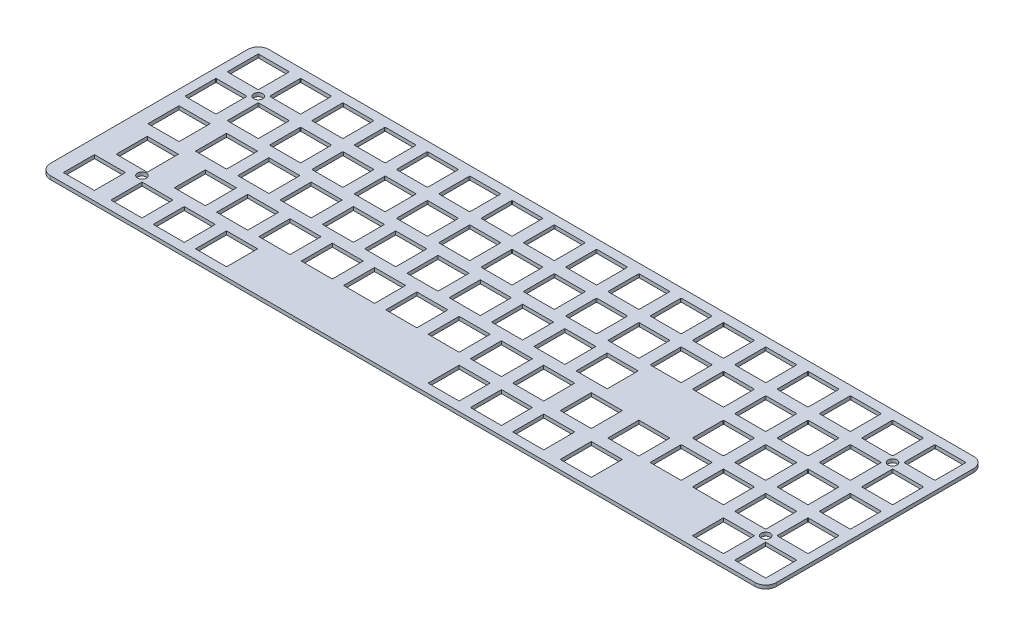
SolidWorks part; units mm, degrees
ref_plane "Front" through (0, 0, 0) normal (0, 0, 1) x (1, 0, 0)
ref_plane "Top" through (0, 0, 0) normal (0, 1, 0) x (1, 0, 0)
ref_plane "Right" through (0, 0, 0) normal (1, 0, 0) x (0, 0, -1)
sketch "Sketch1" plane through (0, 0, 0) normal (0, 1, 0) x (1, 0, 0)
  line L0 (-161.925, 28.575) -> (161.925, 28.575)
  line L1 (161.925, -47.625) -> (-161.925, -47.625)
  line L2 (161.925, -47.625) -> (161.925, 47.625)
  line L3 (161.925, 47.625) -> (-161.925, 47.625)
  line L4 (-161.925, -47.625) -> (-161.925, 47.625)
  line L5 (-123.825, 47.625) -> (-123.825, 28.575)
  line L6 (-104.775, 47.625) -> (-104.775, 28.575)
  line L7 (-142.875, 47.625) -> (-142.875, 28.575)
  line L8 (-85.725, 47.625) -> (-85.725, 28.575)
  line L9 (-66.675, 47.625) -> (-66.675, 28.575)
  line L10 (-47.625, 47.625) -> (-47.625, 28.575)
  line L11 (-28.575, 47.625) -> (-28.575, 28.575)
  line L12 (-9.525, 47.625) -> (-9.525, 28.575)
  line L13 (9.525, 47.625) -> (9.525, 28.575)
  line L14 (28.575, 47.625) -> (28.575, 28.575)
  line L15 (47.625, 47.625) -> (47.625, 28.575)
  line L16 (66.675, 47.625) -> (66.675, 28.575)
  line L17 (85.725, 47.625) -> (85.725, 28.575)
  line L18 (104.775, 47.625) -> (104.775, 28.575)
  line L19 (123.825, 47.625) -> (123.825, 28.575)
  line L20 (142.875, 47.625) -> (142.875, 28.575)
  line L21 (-142.875, 47.625) -> (-123.825, 47.625) construction
  line L22 (-161.925, 9.525) -> (161.925, 9.525)
  line L23 (-142.875, 28.575) -> (-142.875, 9.525)
  line L24 (-123.825, 28.575) -> (-123.825, 9.525)
  line L25 (-104.775, 28.575) -> (-104.775, 9.525)
  line L26 (-85.725, 28.575) -> (-85.725, 9.525)
  line L27 (-66.675, 28.575) -> (-66.675, 9.525)
  line L28 (-47.625, 28.575) -> (-47.625, 9.525)
  line L29 (-28.575, 28.575) -> (-28.575, 9.525)
  line L30 (-9.525, 28.575) -> (-9.525, 9.525)
  line L31 (9.525, 28.575) -> (9.525, 9.525)
  line L32 (28.575, 28.575) -> (28.575, 9.525)
  line L33 (47.625, 28.575) -> (47.625, 9.525)
  line L34 (66.675, 28.575) -> (66.675, 9.525)
  line L35 (85.725, 28.575) -> (85.725, 9.525)
  line L36 (104.775, 28.575) -> (104.775, 9.525)
  line L37 (123.825, 28.575) -> (123.825, 9.525)
  line L38 (142.875, 28.575) -> (142.875, 9.525)
  line L39 (-142.875, 28.575) -> (-123.825, 28.575) construction
  line L40 (-161.925, -9.525) -> (161.925, -9.525)
  line L41 (-161.925, -28.575) -> (161.925, -28.575)
  line L42 (-138.1125, 9.525) -> (-138.1125, -9.525)
  line L43 (-128.5875, -9.525) -> (-128.5875, -28.575)
  line L44 (-138.1125, -28.575) -> (-138.1125, -47.625)
  line L45 (-119.0625, 9.525) -> (-119.0625, -9.525)
  line L46 (-100.0125, 9.525) -> (-100.0125, -9.525)
  line L47 (-80.9625, 9.525) -> (-80.9625, -9.525)
  line L48 (-61.9125, 9.525) -> (-61.9125, -9.525)
  line L49 (-42.8625, 9.525) -> (-42.8625, -9.525)
  line L50 (-23.8125, 9.525) -> (-23.8125, -9.525)
  line L51 (-4.7625, 9.525) -> (-4.7625, -9.525)
  line L52 (14.2875, 9.525) -> (14.2875, -9.525)
  line L53 (33.3375, 9.525) -> (33.3375, -9.525)
  line L54 (-138.1125, 9.525) -> (-119.0625, 9.525) construction
  line L55 (52.3875, 9.525) -> (52.3875, -9.525)
  line L56 (85.725, 9.525) -> (85.725, -9.525)
  line L57 (-109.5375, -9.525) -> (-109.5375, -28.575)
  line L58 (-90.4875, -9.525) -> (-90.4875, -28.575)
  line L59 (-71.4375, -9.525) -> (-71.4375, -28.575)
  line L60 (-52.3875, -9.525) -> (-52.3875, -28.575)
  line L61 (-33.3375, -9.525) -> (-33.3375, -28.575)
  line L62 (-14.2875, -9.525) -> (-14.2875, -28.575)
  line L63 (4.7625, -9.525) -> (4.7625, -28.575)
  line L64 (23.8125, -9.525) -> (23.8125, -28.575)
  line L65 (42.8625, -9.525) -> (42.8625, -28.575)
  line L66 (-128.5875, -9.525) -> (-109.5375, -9.525) construction
  line L67 (66.675, -9.525) -> (66.675, -28.575)
  line L68 (85.725, -9.525) -> (85.725, -28.575)
  line L69 (-119.0625, -28.575) -> (-119.0625, -47.625)
  line L70 (-100.0125, -28.575) -> (-100.0125, -47.625)
  line L71 (-80.9625, -28.575) -> (-80.9625, -47.625)
  line L72 (-138.1125, -28.575) -> (-119.0625, -28.575) construction
  line L73 (-47.625, -28.575) -> (-47.625, -47.625)
  line L74 (4.7625, -28.575) -> (4.7625, -47.625)
  line L75 (23.8125, -28.575) -> (23.8125, -47.625)
  line L76 (42.8625, -28.575) -> (42.8625, -47.625)
  line L77 (61.9125, -28.575) -> (61.9125, -47.625)
  line L78 (85.725, -28.575) -> (85.725, -47.625)
  line L79 (104.775, 9.525) -> (104.775, -9.525)
  line L80 (104.775, -9.525) -> (104.775, -28.575)
  line L81 (123.825, 9.525) -> (123.825, -9.525)
  line L82 (123.825, -9.525) -> (123.825, -28.575)
  line L83 (123.825, -28.575) -> (123.825, -47.625)
  line L84 (142.875, 9.525) -> (142.875, -9.525)
  line L85 (142.875, -9.525) -> (142.875, -28.575)
  line L86 (142.875, -28.575) -> (142.875, -47.625)
  line L87 (-161.925, 47.625) -> (-142.875, 28.575) construction
  line L88 (-142.875, 28.575) -> (-161.925, 9.525) construction
  line L89 (-161.925, 9.525) -> (-138.1125, -9.525) construction
  line L90 (-138.1125, -9.525) -> (-119.0625, 9.525) construction
  line L91 (-119.0625, 9.525) -> (-100.0125, -9.525) construction
  line L92 (-100.0125, -9.525) -> (-80.9625, 9.525) construction
  line L93 (-80.9625, 9.525) -> (-61.9125, -9.525) construction
  line L94 (-61.9125, -9.525) -> (-42.8625, 9.525) construction
  line L95 (-42.8625, 9.525) -> (-23.8125, -9.525) construction
  line L96 (-23.8125, -9.525) -> (-4.7625, 9.525) construction
  line L97 (-4.7625, 9.525) -> (14.2875, -9.525) construction
  line L98 (14.2875, -9.525) -> (33.3375, 9.525) construction
  line L99 (33.3375, 9.525) -> (52.3875, -9.525) construction
  line L100 (52.3875, -9.525) -> (85.725, 9.525) construction
  line L101 (85.725, 9.525) -> (104.775, -9.525) construction
  line L102 (104.775, -9.525) -> (85.725, -28.575) construction
  line L103 (85.725, -47.625) -> (123.825, -28.575) construction
  line L104 (85.725, -28.575) -> (123.825, -47.625) construction
  line L105 (123.825, -28.575) -> (104.775, -9.525) construction
  line L106 (104.775, -9.525) -> (123.825, 9.525) construction
  line L107 (123.825, 9.525) -> (104.775, 28.575) construction
  line L108 (104.775, 28.575) -> (123.825, 47.625) construction
  line L109 (123.825, 47.625) -> (142.875, 28.575) construction
  line L110 (142.875, 28.575) -> (123.825, 9.525) construction
  line L111 (123.825, 9.525) -> (142.875, -9.525) construction
  line L112 (142.875, -9.525) -> (123.825, -28.575) construction
  line L113 (123.825, -28.575) -> (142.875, -47.625) construction
  line L114 (142.875, -47.625) -> (161.925, -28.575) construction
  line L115 (161.925, -28.575) -> (142.875, -9.525) construction
  line L116 (142.875, -9.525) -> (161.925, 9.525) construction
  line L117 (161.925, 9.525) -> (142.875, 28.575) construction
  line L118 (142.875, 28.575) -> (161.925, 47.625) construction
  line L119 (161.925, -47.625) -> (142.875, -28.575) construction
  line L120 (142.875, -28.575) -> (123.825, -47.625) construction
  line L121 (85.725, -47.625) -> (61.9125, -28.575) construction
  line L122 (61.9125, -28.575) -> (42.8625, -47.625) construction
  line L123 (42.8625, -47.625) -> (23.8125, -28.575) construction
  line L124 (23.8125, -28.575) -> (42.8625, -9.525) construction
  line L125 (42.8625, -9.525) -> (66.675, -28.575) construction
  line L126 (66.675, -28.575) -> (85.725, -9.525) construction
  line L127 (85.725, -9.525) -> (104.775, -28.575) construction
  line L128 (104.775, -28.575) -> (123.825, -9.525) construction
  line L129 (123.825, -9.525) -> (142.875, -28.575) construction
  line L130 (142.875, -28.575) -> (161.925, -9.525) construction
  line L131 (161.925, -9.525) -> (142.875, 9.525) construction
  line L132 (142.875, 9.525) -> (123.825, -9.525) construction
  line L133 (123.825, -9.525) -> (104.775, 9.525) construction
  line L134 (104.775, 9.525) -> (85.725, -9.525) construction
  line L135 (85.725, -9.525) -> (52.3875, 9.525) construction
  line L136 (52.3875, 9.525) -> (33.3375, -9.525) construction
  line L137 (33.3375, -9.525) -> (14.2875, 9.525) construction
  line L138 (14.2875, 9.525) -> (-4.7625, -9.525) construction
  line L139 (-4.7625, -9.525) -> (-23.8125, 9.525) construction
  line L140 (-23.8125, 9.525) -> (-42.8625, -9.525) construction
  line L141 (-42.8625, -9.525) -> (-61.9125, 9.525) construction
  line L142 (-61.9125, 9.525) -> (-80.9625, -9.525) construction
  line L143 (-80.9625, -9.525) -> (-100.0125, 9.525) construction
  line L144 (-100.0125, 9.525) -> (-119.0625, -9.525) construction
  line L145 (-119.0625, -9.525) -> (-138.1125, 9.525) construction
  line L146 (-138.1125, 9.525) -> (-161.925, -9.525) construction
  line L147 (-161.925, -9.525) -> (-128.5875, -28.575) construction
  line L148 (-128.5875, -28.575) -> (-109.5375, -9.525) construction
  line L149 (-109.5375, -9.525) -> (-90.4875, -28.575) construction
  line L150 (-90.4875, -28.575) -> (-71.4375, -9.525) construction
  line L151 (-71.4375, -9.525) -> (-52.3875, -28.575) construction
  line L152 (-52.3875, -28.575) -> (-33.3375, -9.525) construction
  line L153 (-33.3375, -9.525) -> (-14.2875, -28.575) construction
  line L154 (-14.2875, -28.575) -> (4.7625, -9.525) construction
  line L155 (4.7625, -9.525) -> (23.8125, -28.575) construction
  line L156 (23.8125, -28.575) -> (4.7625, -47.625) construction
  line L157 (4.7625, -47.625) -> (-47.625, -28.575) construction
  line L158 (-47.625, -28.575) -> (-80.9625, -47.625) construction
  line L159 (-80.9625, -47.625) -> (-100.0125, -28.575) construction
  line L160 (-100.0125, -28.575) -> (-119.0625, -47.625) construction
  line L161 (-119.0625, -47.625) -> (-138.1125, -28.575) construction
  line L162 (-138.1125, -28.575) -> (-161.925, -47.625) construction
  line L163 (-161.925, -28.575) -> (-138.1125, -47.625) construction
  line L164 (-138.1125, -47.625) -> (-119.0625, -28.575) construction
  line L165 (-119.0625, -28.575) -> (-100.0125, -47.625) construction
  line L166 (-100.0125, -47.625) -> (-80.9625, -28.575) construction
  line L167 (-80.9625, -28.575) -> (-47.625, -47.625) construction
  line L168 (-47.625, -47.625) -> (4.7625, -28.575) construction
  line L169 (4.7625, -28.575) -> (23.8125, -47.625) construction
  line L170 (23.8125, -47.625) -> (42.8625, -28.575) construction
  line L171 (42.8625, -28.575) -> (61.9125, -47.625) construction
  line L172 (61.9125, -47.625) -> (85.725, -28.575) construction
  line L173 (85.725, -28.575) -> (66.675, -9.525) construction
  line L174 (66.675, -9.525) -> (42.8625, -28.575) construction
  line L175 (42.8625, -28.575) -> (23.8125, -9.525) construction
  line L176 (23.8125, -9.525) -> (4.7625, -28.575) construction
  line L177 (4.7625, -28.575) -> (-14.2875, -9.525) construction
  line L178 (-14.2875, -9.525) -> (-33.3375, -28.575) construction
  line L179 (-33.3375, -28.575) -> (-52.3875, -9.525) construction
  line L180 (-52.3875, -9.525) -> (-71.4375, -28.575) construction
  line L181 (-71.4375, -28.575) -> (-90.4875, -9.525) construction
  line L182 (-90.4875, -9.525) -> (-109.5375, -28.575) construction
  line L183 (-109.5375, -28.575) -> (-128.5875, -9.525) construction
  line L184 (-128.5875, -9.525) -> (-161.925, -28.575) construction
  line L185 (161.925, 28.575) -> (142.875, 9.525) construction
  line L186 (142.875, 9.525) -> (123.825, 28.575) construction
  line L187 (123.825, 28.575) -> (104.775, 9.525) construction
  line L188 (104.775, 9.525) -> (85.725, 28.575) construction
  line L189 (85.725, 28.575) -> (66.675, 9.525) construction
  line L190 (66.675, 9.525) -> (47.625, 28.575) construction
  line L191 (47.625, 28.575) -> (28.575, 9.525) construction
  line L192 (28.575, 9.525) -> (9.525, 28.575) construction
  line L193 (9.525, 28.575) -> (-9.525, 9.525) construction
  line L194 (-9.525, 9.525) -> (-28.575, 28.575) construction
  line L195 (-28.575, 28.575) -> (-47.625, 9.525) construction
  line L196 (-47.625, 9.525) -> (-66.675, 28.575) construction
  line L197 (-66.675, 28.575) -> (-85.725, 9.525) construction
  line L198 (-85.725, 9.525) -> (-104.775, 28.575) construction
  line L199 (-104.775, 28.575) -> (-123.825, 9.525) construction
  line L200 (-123.825, 9.525) -> (-142.875, 28.575) construction
  line L201 (-161.925, 28.575) -> (-142.875, 9.525) construction
  line L202 (-142.875, 9.525) -> (-123.825, 28.575) construction
  line L203 (-123.825, 28.575) -> (-104.775, 9.525) construction
  line L204 (-104.775, 9.525) -> (-85.725, 28.575) construction
  line L205 (-85.725, 28.575) -> (-66.675, 9.525) construction
  line L206 (-66.675, 9.525) -> (-47.625, 28.575) construction
  line L207 (-47.625, 28.575) -> (-28.575, 9.525) construction
  line L208 (-28.575, 9.525) -> (-9.525, 28.575) construction
  line L209 (-9.525, 28.575) -> (9.525, 9.525) construction
  line L210 (9.525, 9.525) -> (28.575, 28.575) construction
  line L211 (28.575, 28.575) -> (47.625, 9.525) construction
  line L212 (47.625, 9.525) -> (66.675, 28.575) construction
  line L213 (66.675, 28.575) -> (85.725, 9.525) construction
  line L214 (85.725, 9.525) -> (104.775, 28.575) construction
  line L215 (161.925, 28.575) -> (142.875, 47.625) construction
  line L216 (142.875, 47.625) -> (123.825, 28.575) construction
  line L217 (123.825, 28.575) -> (104.775, 47.625) construction
  line L218 (104.775, 47.625) -> (85.725, 28.575) construction
  line L219 (85.725, 28.575) -> (66.675, 47.625) construction
  line L220 (66.675, 47.625) -> (47.625, 28.575) construction
  line L221 (47.625, 28.575) -> (28.575, 47.625) construction
  line L222 (28.575, 47.625) -> (9.525, 28.575) construction
  line L223 (9.525, 28.575) -> (-9.525, 47.625) construction
  line L224 (-9.525, 47.625) -> (-28.575, 28.575) construction
  line L225 (-28.575, 28.575) -> (-47.625, 47.625) construction
  line L226 (-47.625, 47.625) -> (-66.675, 28.575) construction
  line L227 (-66.675, 28.575) -> (-85.725, 47.625) construction
  line L228 (-85.725, 47.625) -> (-104.775, 28.575) construction
  line L229 (-104.775, 28.575) -> (-123.825, 47.625) construction
  line L230 (-123.825, 47.625) -> (-142.875, 28.575) construction
  line L231 (-161.925, 28.575) -> (-142.875, 47.625) construction
  line L232 (-142.875, 47.625) -> (-123.825, 28.575) construction
  line L233 (-123.825, 28.575) -> (-104.775, 47.625) construction
  line L234 (-104.775, 47.625) -> (-85.725, 28.575) construction
  line L235 (-85.725, 28.575) -> (-66.675, 47.625) construction
  line L236 (-66.675, 47.625) -> (-47.625, 28.575) construction
  line L237 (-47.625, 28.575) -> (-28.575, 47.625) construction
  line L238 (-28.575, 47.625) -> (-9.525, 28.575) construction
  line L239 (-9.525, 28.575) -> (9.525, 47.625) construction
  line L240 (9.525, 47.625) -> (28.575, 28.575) construction
  line L241 (28.575, 28.575) -> (47.625, 47.625) construction
  line L242 (47.625, 47.625) -> (66.675, 28.575) construction
  line L243 (66.675, 28.575) -> (85.725, 47.625) construction
  line L244 (85.725, 47.625) -> (104.775, 28.575) construction
  line L245 (160.147, 50.6095) -> (-160.147, 50.6095)
  line L246 (164.9095, 45.847) -> (164.9095, -45.847)
  line L247 (160.147, -50.6095) -> (-160.147, -50.6095)
  line L248 (-164.9095, 45.847) -> (-164.9095, -45.847)
  arc A0 (164.9095, 45.847) -> (160.147, 50.6095) centre (160.147, 45.847) ccw
  arc A1 (160.147, -50.6095) -> (164.9095, -45.847) centre (160.147, -45.847) ccw
  arc A2 (-164.9095, -45.847) -> (-160.147, -50.6095) centre (-160.147, -45.847) ccw
  arc A3 (-160.147, 50.6095) -> (-164.9095, 45.847) centre (-160.147, 45.847) ccw
  point P145 (0, 0)
  point P146 (104.775, -38.1)
  point P147 (-152.4, 38.1)
  point P148 (-152.4, 19.05)
  point P149 (-150.0188, 0)
  point P150 (-145.2562, -19.05)
  point P151 (-150.0188, -38.1)
  point P152 (-128.5875, -38.1)
  point P153 (-119.0625, -19.05)
  point P154 (-128.5875, 0)
  point P155 (-133.35, 19.05)
  point P156 (-133.35, 38.1)
  point P157 (-114.3, 38.1)
  point P158 (-114.3, 19.05)
  point P159 (-109.5375, 0)
  point P160 (-100.0125, -19.05)
  point P161 (-90.4875, -38.1)
  point P162 (-109.5375, -38.1)
  point P163 (-64.2938, -38.1)
  point P164 (-21.4312, -38.1)
  point P165 (14.2875, -38.1)
  point P166 (33.3375, -38.1)
  point P167 (52.3875, -38.1)
  point P168 (73.8188, -38.1)
  point P169 (133.35, -38.1)
  point P170 (152.4, -38.1)
  point P171 (152.4, -19.05)
  point P172 (133.35, -19.05)
  point P173 (114.3, -19.05)
  point P174 (95.25, -19.05)
  point P175 (76.2, -19.05)
  point P176 (54.7687, -19.05)
  point P177 (33.3375, -19.05)
  point P178 (14.2875, -19.05)
  point P179 (-4.7625, -19.05)
  point P180 (-23.8125, -19.05)
  point P181 (-42.8625, -19.05)
  point P182 (-61.9125, -19.05)
  point P183 (-80.9625, -19.05)
  point P184 (-90.4875, 0)
  point P185 (-71.4375, 0)
  point P186 (-52.3875, 0)
  point P187 (-33.3375, 0)
  point P188 (-14.2875, 0)
  point P189 (4.7625, 0)
  point P190 (23.8125, 0)
  point P191 (42.8625, 0)
  point P192 (69.0563, 0)
  point P193 (95.25, 0)
  point P194 (114.3, 0)
  point P195 (133.35, 0)
  point P196 (152.4, 0)
  point P197 (152.4, 19.05)
  point P198 (133.35, 19.05)
  point P199 (114.3, 19.05)
  point P200 (95.25, 19.05)
  point P201 (76.2, 19.05)
  point P202 (57.15, 19.05)
  point P203 (38.1, 19.05)
  point P204 (19.05, 19.05)
  point P205 (0, 19.05)
  point P206 (-19.05, 19.05)
  point P207 (-38.1, 19.05)
  point P208 (-57.15, 19.05)
  point P209 (-76.2, 19.05)
  point P210 (-95.25, 19.05)
  point P211 (-95.25, 38.1)
  point P212 (-76.2, 38.1)
  point P213 (-57.15, 38.1)
  point P214 (-38.1, 38.1)
  point P215 (-19.05, 38.1)
  point P216 (0, 38.1)
  point P217 (19.05, 38.1)
  point P218 (38.1, 38.1)
  point P219 (57.15, 38.1)
  point P220 (76.2, 38.1)
  point P221 (95.25, 38.1)
  point P222 (114.3, 38.1)
  point P223 (133.35, 38.1)
  point P224 (152.4, 38.1)
  point P225 (-152.4, 38.1)
  point P226 (0, 0)
sketch "Sketch2" plane through (0, 0, 0) normal (0, 1, 0) x (1, 0, 0)
  line L0 (-161.925, 28.575) -> (-142.875, 47.625) construction
  line L1 (-145.7071, 45.0977) -> (-159.0929, 45.0977)
  line L2 (-145.4023, 44.7929) -> (-145.4023, 31.4071)
  line L3 (-145.7071, 31.1023) -> (-159.0929, 31.1023)
  line L4 (-159.3977, 44.7929) -> (-159.3977, 31.4071)
  line L5 (-152.4, 31.1023) -> (-152.4, 45.0977) construction
  line L6 (-145.4023, 38.1) -> (-159.3977, 38.1) construction
  line L7 (-126.3523, 38.1) -> (-140.3477, 38.1) construction
  line L8 (-133.35, 31.1023) -> (-133.35, 45.0977) construction
  line L9 (-126.6571, 45.0977) -> (-140.0429, 45.0977)
  line L10 (-126.3523, 44.7929) -> (-126.3523, 31.4071)
  line L11 (-140.3477, 44.7929) -> (-140.3477, 31.4071)
  line L12 (-126.6571, 31.1023) -> (-140.0429, 31.1023)
  line L13 (-107.3023, 38.1) -> (-121.2977, 38.1) construction
  line L14 (-114.3, 31.1023) -> (-114.3, 45.0977) construction
  line L15 (-107.6071, 45.0977) -> (-120.9929, 45.0977)
  line L16 (-107.3023, 44.7929) -> (-107.3023, 31.4071)
  line L17 (-121.2977, 44.7929) -> (-121.2977, 31.4071)
  line L18 (-107.6071, 31.1023) -> (-120.9929, 31.1023)
  line L19 (-88.2523, 38.1) -> (-102.2477, 38.1) construction
  line L20 (-95.25, 31.1023) -> (-95.25, 45.0977) construction
  line L21 (-88.5571, 45.0977) -> (-101.9429, 45.0977)
  line L22 (-88.2523, 44.7929) -> (-88.2523, 31.4071)
  line L23 (-102.2477, 44.7929) -> (-102.2477, 31.4071)
  line L24 (-88.5571, 31.1023) -> (-101.9429, 31.1023)
  line L25 (-69.2023, 38.1) -> (-83.1977, 38.1) construction
  line L26 (-76.2, 31.1023) -> (-76.2, 45.0977) construction
  line L27 (-69.5071, 45.0977) -> (-82.8929, 45.0977)
  line L28 (-69.2023, 44.7929) -> (-69.2023, 31.4071)
  line L29 (-83.1977, 44.7929) -> (-83.1977, 31.4071)
  line L30 (-69.5071, 31.1023) -> (-82.8929, 31.1023)
  line L31 (-50.1523, 38.1) -> (-64.1477, 38.1) construction
  line L32 (-57.15, 31.1023) -> (-57.15, 45.0977) construction
  line L33 (-50.4571, 45.0977) -> (-63.8429, 45.0977)
  line L34 (-50.1523, 44.7929) -> (-50.1523, 31.4071)
  line L35 (-64.1477, 44.7929) -> (-64.1477, 31.4071)
  line L36 (-50.4571, 31.1023) -> (-63.8429, 31.1023)
  line L37 (-31.1023, 38.1) -> (-45.0977, 38.1) construction
  line L38 (-38.1, 31.1023) -> (-38.1, 45.0977) construction
  line L39 (-31.4071, 45.0977) -> (-44.7929, 45.0977)
  line L40 (-31.1023, 44.7929) -> (-31.1023, 31.4071)
  line L41 (-45.0977, 44.7929) -> (-45.0977, 31.4071)
  line L42 (-31.4071, 31.1023) -> (-44.7929, 31.1023)
  line L43 (-12.0523, 38.1) -> (-26.0477, 38.1) construction
  line L44 (-19.05, 31.1023) -> (-19.05, 45.0977) construction
  line L45 (-12.3571, 45.0977) -> (-25.7429, 45.0977)
  line L46 (-12.0523, 44.7929) -> (-12.0523, 31.4071)
  line L47 (-26.0477, 44.7929) -> (-26.0477, 31.4071)
  line L48 (-12.3571, 31.1023) -> (-25.7429, 31.1023)
  line L49 (6.9977, 38.1) -> (-6.9977, 38.1) construction
  line L50 (0, 31.1023) -> (0, 45.0977) construction
  line L51 (6.6929, 45.0977) -> (-6.6929, 45.0977)
  line L52 (6.9977, 44.7929) -> (6.9977, 31.4071)
  line L53 (-6.9977, 44.7929) -> (-6.9977, 31.4071)
  line L54 (6.6929, 31.1023) -> (-6.6929, 31.1023)
  line L55 (26.0477, 38.1) -> (12.0523, 38.1) construction
  line L56 (19.05, 31.1023) -> (19.05, 45.0977) construction
  line L57 (25.7429, 45.0977) -> (12.3571, 45.0977)
  line L58 (26.0477, 44.7929) -> (26.0477, 31.4071)
  line L59 (12.0523, 44.7929) -> (12.0523, 31.4071)
  line L60 (25.7429, 31.1023) -> (12.3571, 31.1023)
  line L61 (45.0977, 38.1) -> (31.1023, 38.1) construction
  line L62 (38.1, 31.1023) -> (38.1, 45.0977) construction
  line L63 (44.7929, 45.0977) -> (31.4071, 45.0977)
  line L64 (45.0977, 44.7929) -> (45.0977, 31.4071)
  line L65 (31.1023, 44.7929) -> (31.1023, 31.4071)
  line L66 (44.7929, 31.1023) -> (31.4071, 31.1023)
  line L67 (64.1477, 38.1) -> (50.1523, 38.1) construction
  line L68 (57.15, 31.1023) -> (57.15, 45.0977) construction
  line L69 (63.8429, 45.0977) -> (50.4571, 45.0977)
  line L70 (64.1477, 44.7929) -> (64.1477, 31.4071)
  line L71 (50.1523, 44.7929) -> (50.1523, 31.4071)
  line L72 (63.8429, 31.1023) -> (50.4571, 31.1023)
  line L73 (83.1977, 38.1) -> (69.2023, 38.1) construction
  line L74 (76.2, 31.1023) -> (76.2, 45.0977) construction
  line L75 (82.8929, 45.0977) -> (69.5071, 45.0977)
  line L76 (83.1977, 44.7929) -> (83.1977, 31.4071)
  line L77 (69.2023, 44.7929) -> (69.2023, 31.4071)
  line L78 (82.8929, 31.1023) -> (69.5071, 31.1023)
  line L79 (102.2477, 38.1) -> (88.2523, 38.1) construction
  line L80 (95.25, 31.1023) -> (95.25, 45.0977) construction
  line L81 (101.9429, 45.0977) -> (88.5571, 45.0977)
  line L82 (102.2477, 44.7929) -> (102.2477, 31.4071)
  line L83 (88.2523, 44.7929) -> (88.2523, 31.4071)
  line L84 (101.9429, 31.1023) -> (88.5571, 31.1023)
  line L85 (121.2977, 38.1) -> (107.3023, 38.1) construction
  line L86 (114.3, 31.1023) -> (114.3, 45.0977) construction
  line L87 (120.9929, 45.0977) -> (107.6071, 45.0977)
  line L88 (121.2977, 44.7929) -> (121.2977, 31.4071)
  line L89 (107.3023, 44.7929) -> (107.3023, 31.4071)
  line L90 (120.9929, 31.1023) -> (107.6071, 31.1023)
  line L91 (140.3477, 38.1) -> (126.3523, 38.1) construction
  line L92 (133.35, 31.1023) -> (133.35, 45.0977) construction
  line L93 (140.0429, 45.0977) -> (126.6571, 45.0977)
  line L94 (140.3477, 44.7929) -> (140.3477, 31.4071)
  line L95 (126.3523, 44.7929) -> (126.3523, 31.4071)
  line L96 (140.0429, 31.1023) -> (126.6571, 31.1023)
  line L97 (159.3977, 38.1) -> (145.4023, 38.1) construction
  line L98 (152.4, 31.1023) -> (152.4, 45.0977) construction
  line L99 (159.0929, 45.0977) -> (145.7071, 45.0977)
  line L100 (159.3977, 44.7929) -> (159.3977, 31.4071)
  line L101 (145.4023, 44.7929) -> (145.4023, 31.4071)
  line L102 (159.0929, 31.1023) -> (145.7071, 31.1023)
  line L103 (-126.3523, 19.05) -> (-140.3477, 19.05) construction
  line L104 (-133.35, 12.0523) -> (-133.35, 26.0477) construction
  line L105 (-126.6571, 26.0477) -> (-140.0429, 26.0477)
  line L106 (-126.3523, 25.7429) -> (-126.3523, 12.3571)
  line L107 (-140.3477, 25.7429) -> (-140.3477, 12.3571)
  line L108 (-126.6571, 12.0523) -> (-140.0429, 12.0523)
  line L109 (-107.3023, 19.05) -> (-121.2977, 19.05) construction
  line L110 (-114.3, 12.0523) -> (-114.3, 26.0477) construction
  line L111 (-107.6071, 26.0477) -> (-120.9929, 26.0477)
  line L112 (-107.3023, 25.7429) -> (-107.3023, 12.3571)
  line L113 (-121.2977, 25.7429) -> (-121.2977, 12.3571)
  line L114 (-107.6071, 12.0523) -> (-120.9929, 12.0523)
  line L115 (-88.2523, 19.05) -> (-102.2477, 19.05) construction
  line L116 (-95.25, 12.0523) -> (-95.25, 26.0477) construction
  line L117 (-88.5571, 26.0477) -> (-101.9429, 26.0477)
  line L118 (-88.2523, 25.7429) -> (-88.2523, 12.3571)
  line L119 (-102.2477, 25.7429) -> (-102.2477, 12.3571)
  line L120 (-88.5571, 12.0523) -> (-101.9429, 12.0523)
  line L121 (-69.2023, 19.05) -> (-83.1977, 19.05) construction
  line L122 (-76.2, 12.0523) -> (-76.2, 26.0477) construction
  line L123 (-69.5071, 26.0477) -> (-82.8929, 26.0477)
  line L124 (-69.2023, 25.7429) -> (-69.2023, 12.3571)
  line L125 (-83.1977, 25.7429) -> (-83.1977, 12.3571)
  line L126 (-69.5071, 12.0523) -> (-82.8929, 12.0523)
  line L127 (-50.1523, 19.05) -> (-64.1477, 19.05) construction
  line L128 (-57.15, 12.0523) -> (-57.15, 26.0477) construction
  line L129 (-50.4571, 26.0477) -> (-63.8429, 26.0477)
  line L130 (-50.1523, 25.7429) -> (-50.1523, 12.3571)
  line L131 (-64.1477, 25.7429) -> (-64.1477, 12.3571)
  line L132 (-50.4571, 12.0523) -> (-63.8429, 12.0523)
  line L133 (-31.1023, 19.05) -> (-45.0977, 19.05) construction
  line L134 (-38.1, 12.0523) -> (-38.1, 26.0477) construction
  line L135 (-31.4071, 26.0477) -> (-44.7929, 26.0477)
  line L136 (-31.1023, 25.7429) -> (-31.1023, 12.3571)
  line L137 (-45.0977, 25.7429) -> (-45.0977, 12.3571)
  line L138 (-31.4071, 12.0523) -> (-44.7929, 12.0523)
  line L139 (-12.0523, 19.05) -> (-26.0477, 19.05) construction
  line L140 (-19.05, 12.0523) -> (-19.05, 26.0477) construction
  line L141 (-12.3571, 26.0477) -> (-25.7429, 26.0477)
  line L142 (-12.0523, 25.7429) -> (-12.0523, 12.3571)
  line L143 (-26.0477, 25.7429) -> (-26.0477, 12.3571)
  line L144 (-12.3571, 12.0523) -> (-25.7429, 12.0523)
  line L145 (6.9977, 19.05) -> (-6.9977, 19.05) construction
  line L146 (0, 12.0523) -> (0, 26.0477) construction
  line L147 (6.6929, 26.0477) -> (-6.6929, 26.0477)
  line L148 (6.9977, 25.7429) -> (6.9977, 12.3571)
  line L149 (-6.9977, 25.7429) -> (-6.9977, 12.3571)
  line L150 (6.6929, 12.0523) -> (-6.6929, 12.0523)
  line L151 (26.0477, 19.05) -> (12.0523, 19.05) construction
  line L152 (19.05, 12.0523) -> (19.05, 26.0477) construction
  line L153 (25.7429, 26.0477) -> (12.3571, 26.0477)
  line L154 (26.0477, 25.7429) -> (26.0477, 12.3571)
  line L155 (12.0523, 25.7429) -> (12.0523, 12.3571)
  line L156 (25.7429, 12.0523) -> (12.3571, 12.0523)
  line L157 (45.0977, 19.05) -> (31.1023, 19.05) construction
  line L158 (38.1, 12.0523) -> (38.1, 26.0477) construction
  line L159 (44.7929, 26.0477) -> (31.4071, 26.0477)
  line L160 (45.0977, 25.7429) -> (45.0977, 12.3571)
  line L161 (31.1023, 25.7429) -> (31.1023, 12.3571)
  line L162 (44.7929, 12.0523) -> (31.4071, 12.0523)
  line L163 (64.1477, 19.05) -> (50.1523, 19.05) construction
  line L164 (57.15, 12.0523) -> (57.15, 26.0477) construction
  line L165 (63.8429, 26.0477) -> (50.4571, 26.0477)
  line L166 (64.1477, 25.7429) -> (64.1477, 12.3571)
  line L167 (50.1523, 25.7429) -> (50.1523, 12.3571)
  line L168 (63.8429, 12.0523) -> (50.4571, 12.0523)
  line L169 (83.1977, 19.05) -> (69.2023, 19.05) construction
  line L170 (76.2, 12.0523) -> (76.2, 26.0477) construction
  line L171 (82.8929, 26.0477) -> (69.5071, 26.0477)
  line L172 (83.1977, 25.7429) -> (83.1977, 12.3571)
  line L173 (69.2023, 25.7429) -> (69.2023, 12.3571)
  line L174 (82.8929, 12.0523) -> (69.5071, 12.0523)
  line L175 (102.2477, 19.05) -> (88.2523, 19.05) construction
  line L176 (95.25, 12.0523) -> (95.25, 26.0477) construction
  line L177 (101.9429, 26.0477) -> (88.5571, 26.0477)
  line L178 (102.2477, 25.7429) -> (102.2477, 12.3571)
  line L179 (88.2523, 25.7429) -> (88.2523, 12.3571)
  line L180 (101.9429, 12.0523) -> (88.5571, 12.0523)
  line L181 (121.2977, 19.05) -> (107.3023, 19.05) construction
  line L182 (114.3, 12.0523) -> (114.3, 26.0477) construction
  line L183 (120.9929, 26.0477) -> (107.6071, 26.0477)
  line L184 (121.2977, 25.7429) -> (121.2977, 12.3571)
  line L185 (107.3023, 25.7429) -> (107.3023, 12.3571)
  line L186 (120.9929, 12.0523) -> (107.6071, 12.0523)
  line L187 (140.3477, 19.05) -> (126.3523, 19.05) construction
  line L188 (133.35, 12.0523) -> (133.35, 26.0477) construction
  line L189 (140.0429, 26.0477) -> (126.6571, 26.0477)
  line L190 (140.3477, 25.7429) -> (140.3477, 12.3571)
  line L191 (126.3523, 25.7429) -> (126.3523, 12.3571)
  line L192 (140.0429, 12.0523) -> (126.6571, 12.0523)
  line L193 (159.3977, 19.05) -> (145.4023, 19.05) construction
  line L194 (152.4, 12.0523) -> (152.4, 26.0477) construction
  line L195 (159.0929, 26.0477) -> (145.7071, 26.0477)
  line L196 (159.3977, 25.7429) -> (159.3977, 12.3571)
  line L197 (145.4023, 25.7429) -> (145.4023, 12.3571)
  line L198 (159.0929, 12.0523) -> (145.7071, 12.0523)
  line L199 (-145.4023, 19.05) -> (-159.3977, 19.05) construction
  line L200 (-152.4, 12.0523) -> (-152.4, 26.0477) construction
  line L201 (-145.7071, 26.0477) -> (-159.0929, 26.0477)
  line L202 (-145.4023, 25.7429) -> (-145.4023, 12.3571)
  line L203 (-159.3977, 25.7429) -> (-159.3977, 12.3571)
  line L204 (-145.7071, 12.0523) -> (-159.0929, 12.0523)
  line L205 (-100.0125, -26.0477) -> (-100.0125, -12.0523) construction
  line L210 (-138.1125, 9.525) -> (-161.925, -9.525) construction
  line L211 (-157.0164, -6.9977) -> (-143.021, -6.9977)
  line L212 (-157.0164, -6.9977) -> (-157.0164, 6.9977)
  line L213 (-138.2585, -12.0523) -> (-152.254, -12.0523)
  line L214 (-138.2585, -12.0523) -> (-138.2585, -26.0477)
  line L215 (-138.2585, -26.0477) -> (-152.254, -26.0477)
  line L216 (-152.254, -12.0523) -> (-152.254, -26.0477)
  line L217 (-145.2562, -26.0477) -> (-145.2562, -12.0523) construction
  line L218 (-138.2586, -19.05) -> (-152.254, -19.05) construction
  line L219 (-157.0164, 6.9977) -> (-143.021, 6.9977)
  line L220 (-143.021, -6.9977) -> (-143.021, 6.9977)
  line L221 (-150.0187, 6.9977) -> (-150.0187, -6.9977) construction
  line L222 (-157.0164, 0) -> (-143.021, 0) construction
  line L223 (-138.1125, -28.575) -> (-161.925, -47.625) construction
  line L224 (-143.021, -31.1023) -> (-157.0164, -31.1023)
  line L225 (-143.021, -31.1023) -> (-143.021, -45.0977)
  line L226 (-143.021, -45.0977) -> (-157.0164, -45.0977)
  line L227 (-157.0164, -31.1023) -> (-157.0164, -45.0977)
  line L228 (-150.0187, -45.0977) -> (-150.0187, -31.1023) construction
  line L229 (-143.021, -38.1) -> (-157.0164, -38.1) construction
  line L230 (-128.5875, -28.575) -> (-109.5375, -9.525) construction
  line L231 (-121.5898, 6.9977) -> (-135.5852, 6.9977)
  line L232 (-121.5898, 6.9977) -> (-121.5898, -6.9977)
  line L233 (-121.5898, -6.9977) -> (-135.5852, -6.9977)
  line L234 (-135.5852, 6.9977) -> (-135.5852, -6.9977)
  line L235 (-128.5875, -6.9977) -> (-128.5875, 6.9977) construction
  line L236 (-121.5898, 0) -> (-135.5852, 0) construction
  line L237 (-112.0648, -12.0523) -> (-126.0602, -12.0523)
  line L238 (-112.0648, -12.0523) -> (-112.0648, -26.0477)
  line L239 (-112.0648, -26.0477) -> (-126.0602, -26.0477)
  line L240 (-126.0602, -12.0523) -> (-126.0602, -26.0477)
  line L241 (-119.0625, -26.0477) -> (-119.0625, -12.0523) construction
  line L242 (-112.0648, -19.05) -> (-126.0602, -19.05) construction
  line L243 (-138.1125, -47.625) -> (-119.0625, -28.575) construction
  line L244 (-135.5852, -45.0977) -> (-121.5898, -45.0977)
  line L245 (-135.5852, -45.0977) -> (-135.5852, -31.1023)
  line L246 (-135.5852, -31.1023) -> (-121.5898, -31.1023)
  line L247 (-121.5898, -45.0977) -> (-121.5898, -31.1023)
  line L248 (-128.5875, -31.1023) -> (-128.5875, -45.0977) construction
  line L249 (-135.5852, -38.1) -> (-121.5898, -38.1) construction
  line L250 (-102.5398, -6.9977) -> (-116.5352, -6.9977)
  line L251 (-102.5398, 6.9977) -> (-102.5398, -6.9977)
  line L252 (-102.5398, 6.9977) -> (-116.5352, 6.9977)
  line L253 (-116.5352, 6.9977) -> (-116.5352, -6.9977)
  line L254 (-102.5398, 0) -> (-116.5352, 0) construction
  line L255 (-109.5375, -6.9977) -> (-109.5375, 6.9977) construction
  line L256 (-83.4898, -6.9977) -> (-97.4852, -6.9977)
  line L257 (-83.4898, 6.9977) -> (-83.4898, -6.9977)
  line L258 (-83.4898, 6.9977) -> (-97.4852, 6.9977)
  line L259 (-97.4852, 6.9977) -> (-97.4852, -6.9977)
  line L260 (-83.4898, 0) -> (-97.4852, 0) construction
  line L261 (-90.4875, -6.9977) -> (-90.4875, 6.9977) construction
  line L262 (-64.4398, -6.9977) -> (-78.4352, -6.9977)
  line L263 (-64.4398, 6.9977) -> (-64.4398, -6.9977)
  line L264 (-64.4398, 6.9977) -> (-78.4352, 6.9977)
  line L265 (-78.4352, 6.9977) -> (-78.4352, -6.9977)
  line L266 (-64.4398, 0) -> (-78.4352, 0) construction
  line L267 (-71.4375, -6.9977) -> (-71.4375, 6.9977) construction
  line L268 (-45.3898, -6.9977) -> (-59.3852, -6.9977)
  line L269 (-45.3898, 6.9977) -> (-45.3898, -6.9977)
  line L270 (-45.3898, 6.9977) -> (-59.3852, 6.9977)
  line L271 (-59.3852, 6.9977) -> (-59.3852, -6.9977)
  line L272 (-45.3898, 0) -> (-59.3852, 0) construction
  line L273 (-52.3875, -6.9977) -> (-52.3875, 6.9977) construction
  line L274 (-26.3398, -6.9977) -> (-40.3352, -6.9977)
  line L275 (-26.3398, 6.9977) -> (-26.3398, -6.9977)
  line L276 (-26.3398, 6.9977) -> (-40.3352, 6.9977)
  line L277 (-40.3352, 6.9977) -> (-40.3352, -6.9977)
  line L278 (-26.3398, 0) -> (-40.3352, 0) construction
  line L279 (-33.3375, -6.9977) -> (-33.3375, 6.9977) construction
  line L280 (-7.2898, -6.9977) -> (-21.2852, -6.9977)
  line L281 (-7.2898, 6.9977) -> (-7.2898, -6.9977)
  line L282 (-7.2898, 6.9977) -> (-21.2852, 6.9977)
  line L283 (-21.2852, 6.9977) -> (-21.2852, -6.9977)
  line L284 (-7.2898, 0) -> (-21.2852, 0) construction
  line L285 (-14.2875, -6.9977) -> (-14.2875, 6.9977) construction
  line L286 (11.7602, -6.9977) -> (-2.2352, -6.9977)
  line L287 (11.7602, 6.9977) -> (11.7602, -6.9977)
  line L288 (11.7602, 6.9977) -> (-2.2352, 6.9977)
  line L289 (-2.2352, 6.9977) -> (-2.2352, -6.9977)
  line L290 (11.7602, 0) -> (-2.2352, 0) construction
  line L291 (4.7625, -6.9977) -> (4.7625, 6.9977) construction
  line L292 (30.8102, -6.9977) -> (16.8148, -6.9977)
  line L293 (30.8102, 6.9977) -> (30.8102, -6.9977)
  line L294 (30.8102, 6.9977) -> (16.8148, 6.9977)
  line L295 (16.8148, 6.9977) -> (16.8148, -6.9977)
  line L296 (30.8102, 0) -> (16.8148, 0) construction
  line L297 (23.8125, -6.9977) -> (23.8125, 6.9977) construction
  line L298 (49.8602, -6.9977) -> (35.8648, -6.9977)
  line L299 (49.8602, 6.9977) -> (49.8602, -6.9977)
  line L300 (49.8602, 6.9977) -> (35.8648, 6.9977)
  line L301 (35.8648, 6.9977) -> (35.8648, -6.9977)
  line L302 (49.8602, 0) -> (35.8648, 0) construction
  line L303 (42.8625, -6.9977) -> (42.8625, 6.9977) construction
  line L304 (-93.0148, -19.05) -> (-107.0102, -19.05) construction
  line L305 (-93.0148, -12.0523) -> (-107.0102, -12.0523)
  line L306 (-93.0148, -12.0523) -> (-93.0148, -26.0477)
  line L307 (-93.0148, -26.0477) -> (-107.0102, -26.0477)
  line L308 (-107.0102, -12.0523) -> (-107.0102, -26.0477)
  line L309 (-80.9625, -26.0477) -> (-80.9625, -12.0523) construction
  line L310 (-73.9648, -19.05) -> (-87.9602, -19.05) construction
  line L311 (-73.9648, -12.0523) -> (-87.9602, -12.0523)
  line L312 (-73.9648, -12.0523) -> (-73.9648, -26.0477)
  line L313 (-73.9648, -26.0477) -> (-87.9602, -26.0477)
  line L314 (-87.9602, -12.0523) -> (-87.9602, -26.0477)
  line L315 (-61.9125, -26.0477) -> (-61.9125, -12.0523) construction
  line L316 (-54.9148, -19.05) -> (-68.9102, -19.05) construction
  line L317 (-54.9148, -12.0523) -> (-68.9102, -12.0523)
  line L318 (-54.9148, -12.0523) -> (-54.9148, -26.0477)
  line L319 (-54.9148, -26.0477) -> (-68.9102, -26.0477)
  line L320 (-68.9102, -12.0523) -> (-68.9102, -26.0477)
  line L321 (-42.8625, -26.0477) -> (-42.8625, -12.0523) construction
  line L322 (-35.8648, -19.05) -> (-49.8602, -19.05) construction
  line L323 (-35.8648, -12.0523) -> (-49.8602, -12.0523)
  line L324 (-35.8648, -12.0523) -> (-35.8648, -26.0477)
  line L325 (-35.8648, -26.0477) -> (-49.8602, -26.0477)
  line L326 (-49.8602, -12.0523) -> (-49.8602, -26.0477)
  line L327 (-23.8125, -26.0477) -> (-23.8125, -12.0523) construction
  line L328 (-16.8148, -19.05) -> (-30.8102, -19.05) construction
  line L329 (-16.8148, -12.0523) -> (-30.8102, -12.0523)
  line L330 (-16.8148, -12.0523) -> (-16.8148, -26.0477)
  line L331 (-16.8148, -26.0477) -> (-30.8102, -26.0477)
  line L332 (-30.8102, -12.0523) -> (-30.8102, -26.0477)
  line L333 (-4.7625, -26.0477) -> (-4.7625, -12.0523) construction
  line L334 (2.2352, -19.05) -> (-11.7602, -19.05) construction
  line L335 (2.2352, -12.0523) -> (-11.7602, -12.0523)
  line L336 (2.2352, -12.0523) -> (2.2352, -26.0477)
  line L337 (2.2352, -26.0477) -> (-11.7602, -26.0477)
  line L338 (-11.7602, -12.0523) -> (-11.7602, -26.0477)
  line L339 (14.2875, -26.0477) -> (14.2875, -12.0523) construction
  line L340 (21.2852, -19.05) -> (7.2898, -19.05) construction
  line L341 (21.2852, -12.0523) -> (7.2898, -12.0523)
  line L342 (21.2852, -12.0523) -> (21.2852, -26.0477)
  line L343 (21.2852, -26.0477) -> (7.2898, -26.0477)
  line L344 (7.2898, -12.0523) -> (7.2898, -26.0477)
  line L345 (33.3375, -26.0477) -> (33.3375, -12.0523) construction
  line L346 (40.3352, -19.05) -> (26.3398, -19.05) construction
  line L347 (40.3352, -12.0523) -> (26.3398, -12.0523)
  line L348 (40.3352, -12.0523) -> (40.3352, -26.0477)
  line L349 (40.3352, -26.0477) -> (26.3398, -26.0477)
  line L350 (26.3398, -12.0523) -> (26.3398, -26.0477)
  line L353 (-100.0125, -28.575) -> (-119.0625, -47.625) construction
  line L354 (-116.5352, -45.0977) -> (-102.5398, -45.0977)
  line L358 (-116.5352, -45.0977) -> (-116.5352, -31.1023)
  line L359 (-116.5352, -31.1023) -> (-102.5398, -31.1023)
  line L362 (-102.5398, -45.0977) -> (-102.5398, -31.1023)
  line L364 (-109.5375, -31.1023) -> (-109.5375, -45.0977) construction
  line L371 (-116.5352, -38.1) -> (-102.5398, -38.1) construction
  line L373 (-100.0125, -47.625) -> (-80.9625, -28.575) construction
  line L376 (-97.4852, -45.0977) -> (-83.4898, -45.0977)
  line L378 (-97.4852, -45.0977) -> (-97.4852, -31.1023)
  line L381 (101.9429, -6.9977) -> (88.5571, -6.9977)
  line L382 (-97.4852, -31.1023) -> (-83.4898, -31.1023)
  line L383 (-83.4898, -45.0977) -> (-83.4898, -31.1023)
  line L384 (-90.4875, -31.1023) -> (-90.4875, -45.0977) construction
  line L385 (-97.4852, -38.1) -> (-83.4898, -38.1) construction
  line L386 (23.8125, -47.625) -> (42.8625, -28.575) construction
  line L387 (7.2898, -45.0977) -> (21.2852, -45.0977)
  line L388 (7.2898, -45.0977) -> (7.2898, -31.1023)
  line L389 (7.2898, -31.1023) -> (21.2852, -31.1023)
  line L390 (21.2852, -45.0977) -> (21.2852, -31.1023)
  line L391 (14.2875, -31.1023) -> (14.2875, -45.0977) construction
  line L392 (7.2898, -38.1) -> (21.2852, -38.1) construction
  line L393 (26.3398, -45.0977) -> (40.3352, -45.0977)
  line L394 (26.3398, -45.0977) -> (26.3398, -31.1023)
  line L395 (26.3398, -31.1023) -> (40.3352, -31.1023)
  line L396 (40.3352, -45.0977) -> (40.3352, -31.1023)
  line L397 (33.3375, -31.1023) -> (33.3375, -45.0977) construction
  line L398 (26.3398, -38.1) -> (40.3352, -38.1) construction
  line L399 (61.9125, -28.575) -> (42.8625, -47.625) construction
  line L400 (45.3898, -45.0977) -> (59.3852, -45.0977)
  line L401 (45.3898, -45.0977) -> (45.3898, -31.1023)
  line L402 (45.3898, -31.1023) -> (59.3852, -31.1023)
  line L403 (59.3852, -45.0977) -> (59.3852, -31.1023)
  line L404 (52.3875, -31.1023) -> (52.3875, -45.0977) construction
  line L405 (45.3898, -38.1) -> (59.3852, -38.1) construction
  line L406 (102.2477, 6.6929) -> (102.2477, -6.6929)
  line L407 (66.821, -45.0977) -> (80.8165, -45.0977)
  line L408 (66.821, -45.0977) -> (66.821, -31.1023)
  line L409 (66.821, -31.1023) -> (80.8165, -31.1023)
  line L410 (80.8165, -45.0977) -> (80.8165, -31.1023)
  line L411 (73.8188, -31.1023) -> (73.8188, -45.0977) construction
  line L412 (66.821, -38.1) -> (80.8165, -38.1) construction
  line L413 (101.9429, 6.9977) -> (88.5571, 6.9977)
  line L414 (88.2523, 6.6929) -> (88.2523, -6.6929)
  line L415 (95.25, -6.9977) -> (95.25, 6.9977) construction
  line L416 (102.2477, 0) -> (88.2523, 0) construction
  line L417 (120.9929, -6.9977) -> (107.6071, -6.9977)
  line L418 (114.3, -6.9977) -> (114.3, 6.9977) construction
  line L419 (121.2977, 0) -> (107.3023, 0) construction
  line L420 (120.9929, 6.9977) -> (107.6071, 6.9977)
  line L421 (107.3023, 6.6929) -> (107.3023, -6.6929)
  line L422 (121.2977, 6.6929) -> (121.2977, -6.6929)
  line L423 (140.0429, 6.9977) -> (126.6571, 6.9977)
  line L424 (126.3523, 6.6929) -> (126.3523, -6.6929)
  line L425 (133.35, -6.9977) -> (133.35, 6.9977) construction
  line L426 (140.3477, 0) -> (126.3523, 0) construction
  line L427 (140.3477, 6.6929) -> (140.3477, -6.6929)
  line L428 (140.0429, -6.9977) -> (126.6571, -6.9977)
  line L429 (159.3977, 6.6929) -> (159.3977, -6.6929)
  line L430 (159.0929, -6.9977) -> (145.7071, -6.9977)
  line L431 (152.4, -6.9977) -> (152.4, 6.9977) construction
  line L432 (145.4023, 6.6929) -> (145.4023, -6.6929)
  line L433 (159.3977, 0) -> (145.4023, 0) construction
  line L434 (159.0929, 6.9977) -> (145.7071, 6.9977)
  line L435 (101.9429, -26.0477) -> (88.5571, -26.0477)
  line L436 (102.2477, -12.3571) -> (102.2477, -25.7429)
  line L437 (101.9429, -12.0523) -> (88.5571, -12.0523)
  line L438 (88.2523, -12.3571) -> (88.2523, -25.7429)
  line L439 (95.25, -26.0477) -> (95.25, -12.0523) construction
  line L440 (102.2477, -19.05) -> (88.2523, -19.05) construction
  line L441 (120.9929, -26.0477) -> (107.6071, -26.0477)
  line L442 (114.3, -26.0477) -> (114.3, -12.0523) construction
  line L443 (121.2977, -19.05) -> (107.3023, -19.05) construction
  line L444 (120.9929, -12.0523) -> (107.6071, -12.0523)
  line L445 (107.3023, -12.3571) -> (107.3023, -25.7429)
  line L446 (121.2977, -12.3571) -> (121.2977, -25.7429)
  line L447 (140.0429, -12.0523) -> (126.6571, -12.0523)
  line L448 (126.3523, -12.3571) -> (126.3523, -25.7429)
  line L449 (133.35, -26.0477) -> (133.35, -12.0523) construction
  line L450 (140.3477, -19.05) -> (126.3523, -19.05) construction
  line L451 (140.3477, -12.3571) -> (140.3477, -25.7429)
  line L452 (140.0429, -26.0477) -> (126.6571, -26.0477)
  line L453 (159.3977, -12.3571) -> (159.3977, -25.7429)
  line L454 (159.0929, -26.0477) -> (145.7071, -26.0477)
  line L455 (152.4, -26.0477) -> (152.4, -12.0523) construction
  line L456 (145.4023, -12.3571) -> (145.4023, -25.7429)
  line L457 (159.3977, -19.05) -> (145.4023, -19.05) construction
  line L458 (159.0929, -12.0523) -> (145.7071, -12.0523)
  line L459 (85.725, -28.575) -> (66.675, -9.525) construction
  line L460 (145.4023, -45.0977) -> (159.3977, -45.0977)
  line L461 (145.4023, -45.0977) -> (145.4023, -31.1023)
  line L462 (145.4023, -31.1023) -> (159.3977, -31.1023)
  line L463 (159.3977, -45.0977) -> (159.3977, -31.1023)
  line L464 (152.4, -31.1023) -> (152.4, -45.0977) construction
  line L465 (145.4023, -38.1) -> (159.3977, -38.1) construction
  line L466 (126.3523, -45.0977) -> (140.3477, -45.0977)
  line L467 (126.3523, -45.0977) -> (126.3523, -31.1023)
  line L468 (126.3523, -31.1023) -> (140.3477, -31.1023)
  line L469 (140.3477, -45.0977) -> (140.3477, -31.1023)
  line L470 (133.35, -31.1023) -> (133.35, -45.0977) construction
  line L471 (126.3523, -38.1) -> (140.3477, -38.1) construction
  line L472 (69.2023, -26.0477) -> (83.1977, -26.0477)
  line L473 (69.2023, -26.0477) -> (69.2023, -12.0523)
  line L474 (69.2023, -12.0523) -> (83.1977, -12.0523)
  line L475 (83.1977, -26.0477) -> (83.1977, -12.0523)
  line L476 (76.2, -12.0523) -> (76.2, -26.0477) construction
  line L477 (69.2023, -19.05) -> (83.1977, -19.05) construction
  line L478 (-145.7071, 31.4071) -> (-140.0429, 25.7429) construction
  line L479 (47.771, -26.0477) -> (61.7665, -26.0477)
  line L480 (47.771, -26.0477) -> (47.771, -12.0523)
  line L481 (47.771, -12.0523) -> (61.7665, -12.0523)
  line L482 (61.7665, -26.0477) -> (61.7665, -12.0523)
  line L483 (54.7687, -12.0523) -> (54.7687, -26.0477) construction
  line L484 (47.771, -19.05) -> (61.7665, -19.05) construction
  line L489 (-140.0429, 31.4071) -> (-145.7071, 25.7429) construction
  line L490 (158.75, -49.2125) -> (-158.75, -49.2125)
  line L491 (140.0429, 31.4071) -> (145.7071, 25.7429) construction
  line L496 (163.5125, -44.45) -> (163.5125, 44.45)
  line L497 (158.75, 49.2125) -> (-158.75, 49.2125)
  line L498 (145.7071, 31.4071) -> (140.0429, 25.7429) construction
  line L503 (-163.5125, -44.45) -> (-163.5125, 44.45)
  line L504 (0, 49.2125) -> (0, -49.2125) construction
  line L510 (163.5125, 0) -> (-163.5125, 0) construction
  arc A0 (-145.4023, 31.4071) -> (-145.7071, 31.1023) centre (-145.7071, 31.4071) cw
  arc A1 (-145.7071, 45.0977) -> (-145.4023, 44.7929) centre (-145.7071, 44.7929) cw
  arc A2 (-159.0929, 45.0977) -> (-159.3977, 44.7929) centre (-159.0929, 44.7929) ccw
  arc A3 (-159.0929, 31.1023) -> (-159.3977, 31.4071) centre (-159.0929, 31.4071) cw
  arc A4 (-126.6571, 45.0977) -> (-126.3523, 44.7929) centre (-126.6571, 44.7929) cw
  arc A5 (-140.0429, 45.0977) -> (-140.3477, 44.7929) centre (-140.0429, 44.7929) ccw
  arc A6 (-140.0429, 31.1023) -> (-140.3477, 31.4071) centre (-140.0429, 31.4071) cw
  arc A7 (-126.3523, 31.4071) -> (-126.6571, 31.1023) centre (-126.6571, 31.4071) cw
  arc A8 (-107.6071, 45.0977) -> (-107.3023, 44.7929) centre (-107.6071, 44.7929) cw
  arc A9 (-120.9929, 45.0977) -> (-121.2977, 44.7929) centre (-120.9929, 44.7929) ccw
  arc A10 (-120.9929, 31.1023) -> (-121.2977, 31.4071) centre (-120.9929, 31.4071) cw
  arc A11 (-107.3023, 31.4071) -> (-107.6071, 31.1023) centre (-107.6071, 31.4071) cw
  arc A12 (-88.5571, 45.0977) -> (-88.2523, 44.7929) centre (-88.5571, 44.7929) cw
  arc A13 (-101.9429, 45.0977) -> (-102.2477, 44.7929) centre (-101.9429, 44.7929) ccw
  arc A14 (-101.9429, 31.1023) -> (-102.2477, 31.4071) centre (-101.9429, 31.4071) cw
  arc A15 (-88.2523, 31.4071) -> (-88.5571, 31.1023) centre (-88.5571, 31.4071) cw
  arc A16 (-69.5071, 45.0977) -> (-69.2023, 44.7929) centre (-69.5071, 44.7929) cw
  arc A17 (-82.8929, 45.0977) -> (-83.1977, 44.7929) centre (-82.8929, 44.7929) ccw
  arc A18 (-82.8929, 31.1023) -> (-83.1977, 31.4071) centre (-82.8929, 31.4071) cw
  arc A19 (-69.2023, 31.4071) -> (-69.5071, 31.1023) centre (-69.5071, 31.4071) cw
  arc A20 (-50.4571, 45.0977) -> (-50.1523, 44.7929) centre (-50.4571, 44.7929) cw
  arc A21 (-63.8429, 45.0977) -> (-64.1477, 44.7929) centre (-63.8429, 44.7929) ccw
  arc A22 (-63.8429, 31.1023) -> (-64.1477, 31.4071) centre (-63.8429, 31.4071) cw
  arc A23 (-50.1523, 31.4071) -> (-50.4571, 31.1023) centre (-50.4571, 31.4071) cw
  arc A24 (-31.4071, 45.0977) -> (-31.1023, 44.7929) centre (-31.4071, 44.7929) cw
  arc A25 (-44.7929, 45.0977) -> (-45.0977, 44.7929) centre (-44.7929, 44.7929) ccw
  arc A26 (-44.7929, 31.1023) -> (-45.0977, 31.4071) centre (-44.7929, 31.4071) cw
  arc A27 (-31.1023, 31.4071) -> (-31.4071, 31.1023) centre (-31.4071, 31.4071) cw
  arc A28 (-12.3571, 45.0977) -> (-12.0523, 44.7929) centre (-12.3571, 44.7929) cw
  arc A29 (-25.7429, 45.0977) -> (-26.0477, 44.7929) centre (-25.7429, 44.7929) ccw
  arc A30 (-25.7429, 31.1023) -> (-26.0477, 31.4071) centre (-25.7429, 31.4071) cw
  arc A31 (-12.0523, 31.4071) -> (-12.3571, 31.1023) centre (-12.3571, 31.4071) cw
  arc A32 (6.6929, 45.0977) -> (6.9977, 44.7929) centre (6.6929, 44.7929) cw
  arc A33 (-6.6929, 45.0977) -> (-6.9977, 44.7929) centre (-6.6929, 44.7929) ccw
  arc A34 (-6.6929, 31.1023) -> (-6.9977, 31.4071) centre (-6.6929, 31.4071) cw
  arc A35 (6.9977, 31.4071) -> (6.6929, 31.1023) centre (6.6929, 31.4071) cw
  arc A36 (25.7429, 45.0977) -> (26.0477, 44.7929) centre (25.7429, 44.7929) cw
  arc A37 (12.3571, 45.0977) -> (12.0523, 44.7929) centre (12.3571, 44.7929) ccw
  arc A38 (12.3571, 31.1023) -> (12.0523, 31.4071) centre (12.3571, 31.4071) cw
  arc A39 (26.0477, 31.4071) -> (25.7429, 31.1023) centre (25.7429, 31.4071) cw
  arc A40 (44.7929, 45.0977) -> (45.0977, 44.7929) centre (44.7929, 44.7929) cw
  arc A41 (31.4071, 45.0977) -> (31.1023, 44.7929) centre (31.4071, 44.7929) ccw
  arc A42 (31.4071, 31.1023) -> (31.1023, 31.4071) centre (31.4071, 31.4071) cw
  arc A43 (45.0977, 31.4071) -> (44.7929, 31.1023) centre (44.7929, 31.4071) cw
  arc A44 (63.8429, 45.0977) -> (64.1477, 44.7929) centre (63.8429, 44.7929) cw
  arc A45 (50.4571, 45.0977) -> (50.1523, 44.7929) centre (50.4571, 44.7929) ccw
  arc A46 (50.4571, 31.1023) -> (50.1523, 31.4071) centre (50.4571, 31.4071) cw
  arc A47 (64.1477, 31.4071) -> (63.8429, 31.1023) centre (63.8429, 31.4071) cw
  arc A48 (82.8929, 45.0977) -> (83.1977, 44.7929) centre (82.8929, 44.7929) cw
  arc A49 (69.5071, 45.0977) -> (69.2023, 44.7929) centre (69.5071, 44.7929) ccw
  arc A50 (69.5071, 31.1023) -> (69.2023, 31.4071) centre (69.5071, 31.4071) cw
  arc A51 (83.1977, 31.4071) -> (82.8929, 31.1023) centre (82.8929, 31.4071) cw
  arc A52 (101.9429, 45.0977) -> (102.2477, 44.7929) centre (101.9429, 44.7929) cw
  arc A53 (88.5571, 45.0977) -> (88.2523, 44.7929) centre (88.5571, 44.7929) ccw
  arc A54 (88.5571, 31.1023) -> (88.2523, 31.4071) centre (88.5571, 31.4071) cw
  arc A55 (102.2477, 31.4071) -> (101.9429, 31.1023) centre (101.9429, 31.4071) cw
  arc A56 (120.9929, 45.0977) -> (121.2977, 44.7929) centre (120.9929, 44.7929) cw
  arc A57 (107.6071, 45.0977) -> (107.3023, 44.7929) centre (107.6071, 44.7929) ccw
  arc A58 (107.6071, 31.1023) -> (107.3023, 31.4071) centre (107.6071, 31.4071) cw
  arc A59 (121.2977, 31.4071) -> (120.9929, 31.1023) centre (120.9929, 31.4071) cw
  arc A60 (140.0429, 45.0977) -> (140.3477, 44.7929) centre (140.0429, 44.7929) cw
  arc A61 (126.6571, 45.0977) -> (126.3523, 44.7929) centre (126.6571, 44.7929) ccw
  arc A62 (126.6571, 31.1023) -> (126.3523, 31.4071) centre (126.6571, 31.4071) cw
  arc A63 (140.3477, 31.4071) -> (140.0429, 31.1023) centre (140.0429, 31.4071) cw
  arc A64 (159.0929, 45.0977) -> (159.3977, 44.7929) centre (159.0929, 44.7929) cw
  arc A65 (145.7071, 45.0977) -> (145.4023, 44.7929) centre (145.7071, 44.7929) ccw
  arc A66 (145.7071, 31.1023) -> (145.4023, 31.4071) centre (145.7071, 31.4071) cw
  arc A67 (159.3977, 31.4071) -> (159.0929, 31.1023) centre (159.0929, 31.4071) cw
  arc A68 (-126.6571, 26.0477) -> (-126.3523, 25.7429) centre (-126.6571, 25.7429) cw
  arc A69 (-140.0429, 26.0477) -> (-140.3477, 25.7429) centre (-140.0429, 25.7429) ccw
  arc A70 (-140.0429, 12.0523) -> (-140.3477, 12.3571) centre (-140.0429, 12.3571) cw
  arc A71 (-126.3523, 12.3571) -> (-126.6571, 12.0523) centre (-126.6571, 12.3571) cw
  arc A72 (-107.6071, 26.0477) -> (-107.3023, 25.7429) centre (-107.6071, 25.7429) cw
  arc A73 (-120.9929, 26.0477) -> (-121.2977, 25.7429) centre (-120.9929, 25.7429) ccw
  arc A74 (-120.9929, 12.0523) -> (-121.2977, 12.3571) centre (-120.9929, 12.3571) cw
  arc A75 (-107.3023, 12.3571) -> (-107.6071, 12.0523) centre (-107.6071, 12.3571) cw
  arc A76 (-88.5571, 26.0477) -> (-88.2523, 25.7429) centre (-88.5571, 25.7429) cw
  arc A77 (-101.9429, 26.0477) -> (-102.2477, 25.7429) centre (-101.9429, 25.7429) ccw
  arc A78 (-101.9429, 12.0523) -> (-102.2477, 12.3571) centre (-101.9429, 12.3571) cw
  arc A79 (-88.2523, 12.3571) -> (-88.5571, 12.0523) centre (-88.5571, 12.3571) cw
  arc A80 (-69.5071, 26.0477) -> (-69.2023, 25.7429) centre (-69.5071, 25.7429) cw
  arc A81 (-82.8929, 26.0477) -> (-83.1977, 25.7429) centre (-82.8929, 25.7429) ccw
  arc A82 (-82.8929, 12.0523) -> (-83.1977, 12.3571) centre (-82.8929, 12.3571) cw
  arc A83 (-69.2023, 12.3571) -> (-69.5071, 12.0523) centre (-69.5071, 12.3571) cw
  arc A84 (-50.4571, 26.0477) -> (-50.1523, 25.7429) centre (-50.4571, 25.7429) cw
  arc A85 (-63.8429, 26.0477) -> (-64.1477, 25.7429) centre (-63.8429, 25.7429) ccw
  arc A86 (-63.8429, 12.0523) -> (-64.1477, 12.3571) centre (-63.8429, 12.3571) cw
  arc A87 (-50.1523, 12.3571) -> (-50.4571, 12.0523) centre (-50.4571, 12.3571) cw
  arc A88 (-31.4071, 26.0477) -> (-31.1023, 25.7429) centre (-31.4071, 25.7429) cw
  arc A89 (-44.7929, 26.0477) -> (-45.0977, 25.7429) centre (-44.7929, 25.7429) ccw
  arc A90 (-44.7929, 12.0523) -> (-45.0977, 12.3571) centre (-44.7929, 12.3571) cw
  arc A91 (-31.1023, 12.3571) -> (-31.4071, 12.0523) centre (-31.4071, 12.3571) cw
  arc A92 (-12.3571, 26.0477) -> (-12.0523, 25.7429) centre (-12.3571, 25.7429) cw
  arc A93 (-25.7429, 26.0477) -> (-26.0477, 25.7429) centre (-25.7429, 25.7429) ccw
  arc A94 (-25.7429, 12.0523) -> (-26.0477, 12.3571) centre (-25.7429, 12.3571) cw
  arc A95 (-12.0523, 12.3571) -> (-12.3571, 12.0523) centre (-12.3571, 12.3571) cw
  arc A96 (6.6929, 26.0477) -> (6.9977, 25.7429) centre (6.6929, 25.7429) cw
  arc A97 (-6.6929, 26.0477) -> (-6.9977, 25.7429) centre (-6.6929, 25.7429) ccw
  arc A98 (-6.6929, 12.0523) -> (-6.9977, 12.3571) centre (-6.6929, 12.3571) cw
  arc A99 (6.9977, 12.3571) -> (6.6929, 12.0523) centre (6.6929, 12.3571) cw
  arc A100 (25.7429, 26.0477) -> (26.0477, 25.7429) centre (25.7429, 25.7429) cw
  arc A101 (12.3571, 26.0477) -> (12.0523, 25.7429) centre (12.3571, 25.7429) ccw
  arc A102 (12.3571, 12.0523) -> (12.0523, 12.3571) centre (12.3571, 12.3571) cw
  arc A103 (26.0477, 12.3571) -> (25.7429, 12.0523) centre (25.7429, 12.3571) cw
  arc A104 (44.7929, 26.0477) -> (45.0977, 25.7429) centre (44.7929, 25.7429) cw
  arc A105 (31.4071, 26.0477) -> (31.1023, 25.7429) centre (31.4071, 25.7429) ccw
  arc A106 (31.4071, 12.0523) -> (31.1023, 12.3571) centre (31.4071, 12.3571) cw
  arc A107 (45.0977, 12.3571) -> (44.7929, 12.0523) centre (44.7929, 12.3571) cw
  arc A108 (63.8429, 26.0477) -> (64.1477, 25.7429) centre (63.8429, 25.7429) cw
  arc A109 (50.4571, 26.0477) -> (50.1523, 25.7429) centre (50.4571, 25.7429) ccw
  arc A110 (50.4571, 12.0523) -> (50.1523, 12.3571) centre (50.4571, 12.3571) cw
  arc A111 (64.1477, 12.3571) -> (63.8429, 12.0523) centre (63.8429, 12.3571) cw
  arc A112 (82.8929, 26.0477) -> (83.1977, 25.7429) centre (82.8929, 25.7429) cw
  arc A113 (69.5071, 26.0477) -> (69.2023, 25.7429) centre (69.5071, 25.7429) ccw
  arc A114 (69.5071, 12.0523) -> (69.2023, 12.3571) centre (69.5071, 12.3571) cw
  arc A115 (83.1977, 12.3571) -> (82.8929, 12.0523) centre (82.8929, 12.3571) cw
  arc A116 (101.9429, 26.0477) -> (102.2477, 25.7429) centre (101.9429, 25.7429) cw
  arc A117 (88.5571, 26.0477) -> (88.2523, 25.7429) centre (88.5571, 25.7429) ccw
  arc A118 (88.5571, 12.0523) -> (88.2523, 12.3571) centre (88.5571, 12.3571) cw
  arc A119 (102.2477, 12.3571) -> (101.9429, 12.0523) centre (101.9429, 12.3571) cw
  arc A120 (120.9929, 26.0477) -> (121.2977, 25.7429) centre (120.9929, 25.7429) cw
  arc A121 (107.6071, 26.0477) -> (107.3023, 25.7429) centre (107.6071, 25.7429) ccw
  arc A122 (107.6071, 12.0523) -> (107.3023, 12.3571) centre (107.6071, 12.3571) cw
  arc A123 (121.2977, 12.3571) -> (120.9929, 12.0523) centre (120.9929, 12.3571) cw
  arc A124 (140.0429, 26.0477) -> (140.3477, 25.7429) centre (140.0429, 25.7429) cw
  arc A125 (126.6571, 26.0477) -> (126.3523, 25.7429) centre (126.6571, 25.7429) ccw
  arc A126 (126.6571, 12.0523) -> (126.3523, 12.3571) centre (126.6571, 12.3571) cw
  arc A127 (140.3477, 12.3571) -> (140.0429, 12.0523) centre (140.0429, 12.3571) cw
  arc A128 (159.0929, 26.0477) -> (159.3977, 25.7429) centre (159.0929, 25.7429) cw
  arc A129 (145.7071, 26.0477) -> (145.4023, 25.7429) centre (145.7071, 25.7429) ccw
  arc A130 (145.7071, 12.0523) -> (145.4023, 12.3571) centre (145.7071, 12.3571) cw
  arc A131 (159.3977, 12.3571) -> (159.0929, 12.0523) centre (159.0929, 12.3571) cw
  arc A132 (-145.7071, 26.0477) -> (-145.4023, 25.7429) centre (-145.7071, 25.7429) cw
  arc A133 (-159.0929, 26.0477) -> (-159.3977, 25.7429) centre (-159.0929, 25.7429) ccw
  arc A134 (-159.0929, 12.0523) -> (-159.3977, 12.3571) centre (-159.0929, 12.3571) cw
  arc A135 (-145.4023, 12.3571) -> (-145.7071, 12.0523) centre (-145.7071, 12.3571) cw
  arc A136 (101.9429, 6.9977) -> (102.2477, 6.6929) centre (101.9429, 6.6929) cw
  arc A137 (107.6071, 6.9977) -> (107.3023, 6.6929) centre (107.6071, 6.6929) ccw
  arc A138 (107.6071, -6.9977) -> (107.3023, -6.6929) centre (107.6071, -6.6929) cw
  arc A139 (102.2477, -6.6929) -> (101.9429, -6.9977) centre (101.9429, -6.6929) cw
  arc A140 (88.5571, -6.9977) -> (88.2523, -6.6929) centre (88.5571, -6.6929) cw
  arc A141 (88.5571, 6.9977) -> (88.2523, 6.6929) centre (88.5571, 6.6929) ccw
  arc A142 (121.2977, -6.6929) -> (120.9929, -6.9977) centre (120.9929, -6.6929) cw
  arc A143 (120.9929, 6.9977) -> (121.2977, 6.6929) centre (120.9929, 6.6929) cw
  arc A144 (126.6571, 6.9977) -> (126.3523, 6.6929) centre (126.6571, 6.6929) ccw
  arc A145 (140.0429, 6.9977) -> (140.3477, 6.6929) centre (140.0429, 6.6929) cw
  arc A146 (140.3477, -6.6929) -> (140.0429, -6.9977) centre (140.0429, -6.6929) cw
  arc A147 (126.6571, -6.9977) -> (126.3523, -6.6929) centre (126.6571, -6.6929) cw
  arc A148 (159.3977, -6.6929) -> (159.0929, -6.9977) centre (159.0929, -6.6929) cw
  arc A149 (145.7071, -6.9977) -> (145.4023, -6.6929) centre (145.7071, -6.6929) cw
  arc A150 (159.0929, 6.9977) -> (159.3977, 6.6929) centre (159.0929, 6.6929) cw
  arc A151 (145.7071, 6.9977) -> (145.4023, 6.6929) centre (145.7071, 6.6929) ccw
  arc A152 (101.9429, -12.0523) -> (102.2477, -12.3571) centre (101.9429, -12.3571) cw
  arc A153 (107.6071, -12.0523) -> (107.3023, -12.3571) centre (107.6071, -12.3571) ccw
  arc A154 (107.6071, -26.0477) -> (107.3023, -25.7429) centre (107.6071, -25.7429) cw
  arc A155 (102.2477, -25.7429) -> (101.9429, -26.0477) centre (101.9429, -25.7429) cw
  arc A156 (88.5571, -26.0477) -> (88.2523, -25.7429) centre (88.5571, -25.7429) cw
  arc A157 (88.5571, -12.0523) -> (88.2523, -12.3571) centre (88.5571, -12.3571) ccw
  arc A158 (121.2977, -25.7429) -> (120.9929, -26.0477) centre (120.9929, -25.7429) cw
  arc A159 (120.9929, -12.0523) -> (121.2977, -12.3571) centre (120.9929, -12.3571) cw
  arc A160 (126.6571, -12.0523) -> (126.3523, -12.3571) centre (126.6571, -12.3571) ccw
  arc A161 (140.0429, -12.0523) -> (140.3477, -12.3571) centre (140.0429, -12.3571) cw
  arc A162 (140.3477, -25.7429) -> (140.0429, -26.0477) centre (140.0429, -25.7429) cw
  arc A163 (126.6571, -26.0477) -> (126.3523, -25.7429) centre (126.6571, -25.7429) cw
  arc A164 (159.3977, -25.7429) -> (159.0929, -26.0477) centre (159.0929, -25.7429) cw
  arc A165 (145.7071, -26.0477) -> (145.4023, -25.7429) centre (145.7071, -25.7429) cw
  arc A166 (159.0929, -12.0523) -> (159.3977, -12.3571) centre (159.0929, -12.3571) cw
  arc A167 (145.7071, -12.0523) -> (145.4023, -12.3571) centre (145.7071, -12.3571) ccw
  arc A168 (163.5125, 44.45) -> (158.75, 49.2125) centre (158.75, 44.45) ccw
  arc A169 (158.75, -49.2125) -> (163.5125, -44.45) centre (158.75, -44.45) ccw
  arc A170 (-158.75, -49.2125) -> (-163.5125, -44.45) centre (-158.75, -44.45) cw
  arc A171 (-158.75, 49.2125) -> (-163.5125, 44.45) centre (-158.75, 44.45) ccw
  circle A172 centre (-142.875, 28.575) radius 2
  circle A173 centre (-138.1125, -28.575) radius 2
  circle A174 centre (142.875, 28.575) radius 2
  circle A175 centre (142.875, -28.575) radius 2
  point P0 (-152.4, 38.1)
  point P15 (-159.3977, 31.1023)
  point P16 (-150.0187, 0)
  point P552 (-109.5375, -38.1)
  point P558 (-145.2562, -19.05)
  point P562 (-150.0187, -38.1)
  point P568 (-128.5875, 0)
  point P572 (-119.0625, -19.05)
  point P578 (-128.5875, -38.1)
  point P759 (-90.4875, -38.1)
  point P765 (14.2875, -38.1)
  point P769 (33.3375, -38.1)
  point P775 (52.3875, -38.1)
  point P781 (73.8188, -38.1)
  point P786 (152.4, -38.1)
  point P950 (133.35, -38.1)
  point P954 (76.2, -19.05)
  point P960 (54.7687, -19.05)
  point P964 (0, 0)
  point P970 (163.5125, 49.2125)
  point P978 (-163.5125, 49.2125)
  point P981 (-142.875, 28.575)
  point P986 (142.875, 28.575)
  point P989 (0, 0)
  point P990 (0, 0)
  dimension "D1" = 0.3048
  dimension "D10" = 4.7625
  dimension "D11" = 4
  dimension "D13" = 4.7625
  dimension "D2" = 13.9954
  dimension "D8" = 327.025
  dimension "D9" = 98.425
  dimension "D12" = 57.15
  dimension "D3" = 17
  dimension "D4" = 2
  dimension "D5" = 10
  dimension "D6" = 9
  dimension "D7" = 3
extrude "Boss-Extrude1" add sketch "Sketch2" along normal mid plane 1.5875
